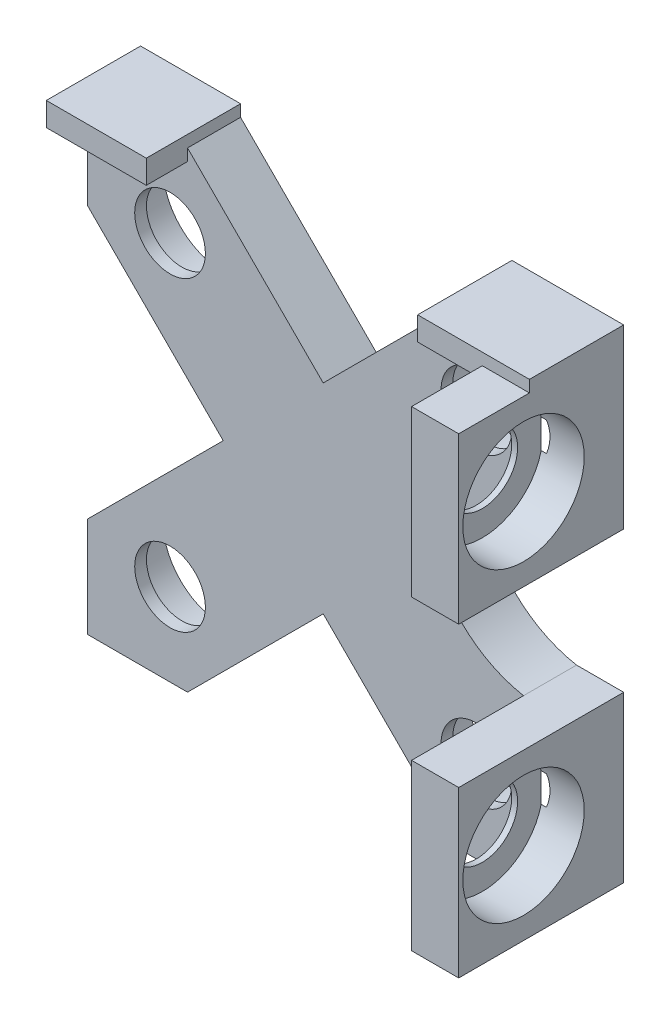
SolidWorks part; units mm, degrees
ref_plane "Plano frontal" through (0, 0, 0) normal (0, 0, 1) x (1, 0, 0)
ref_plane "Plano superior" through (0, 0, 0) normal (0, 1, 0) x (1, 0, 0)
ref_plane "Plano direito" through (0, 0, 0) normal (1, 0, 0) x (0, 0, -1)
sketch "Esboço1" plane through (0, 0, 0) normal (0, 0, 1) x (1, 0, 0)
  line L0 (-8.4853, 0) -> (-20, 11.5147)
  line L1 (-11.5147, 20) -> (-20, 20)
  line L2 (-11.5147, 20) -> (0, 8.4853)
  line L3 (0, 8.4853) -> (0, 0)
  line L4 (0, 0) -> (-8.4853, 0)
  line L5 (-20, 20) -> (-20, 11.5147)
  point P1 (7.079, 9.8915)
  point P3 (0, 0)
  dimension "D1" = 12
  dimension "D2" = 45
  dimension "D3" = 20
extrude "Ressalto-extrusão1" add sketch "Esboço1" along normal blind 4.5
sketch "Esboço2" plane through (0, 0, 4.5) normal (0, 0, 1) x (1, 0, 0)
  line L0 (-20, 20) -> (0, 0) construction
  line L1 (0, 0) -> (0, 8.4853) construction
  circle A0 centre (-13, 13) radius 5.1
  point P6 (-6.6212, 15.1064)
  point P7 (-5.3132, 13.7985)
  dimension "D1" = 10.2
  dimension "D2" = 13
extrude "Corte-extrusão1" cut sketch "Esboço2" along normal blind 3.5 from surface at -4.5 starting at face at (-10, 10, 0)
sketch "Esboço3" plane through (0, 0, 3.5) normal (0, 0, -1) x (-1, 0, 0)
  circle A0 centre (13, 13) radius 3
  dimension "D1" = 6
extrude "Corte-extrusão2" cut sketch "Esboço3" against normal blind 3.5
mirror "Espelhar1" about plane through (0, 0, 0) normal (1, 0, 0) of "Corte-extrusão2", "Corte-extrusão1", "Ressalto-extrusão1"
mirror "Espelhar2" about plane through (0, 0, 0) normal (0, 1, 0) of "Corte-extrusão2", "Ressalto-extrusão1", "Corte-extrusão1", "Espelhar1"
sketch "Esboço5" plane through (20, 0, 0) normal (1, 0, 0) x (0, 0, -1)
  line L0 (-4.5, 20) -> (-4.5, 11.5147) construction
  line L1 (0, 20) -> (-14, 20)
  line L2 (0, 20) -> (0, 6)
  line L3 (0, 6) -> (-14, 6)
  line L4 (-14, 20) -> (-14, 6)
  circle A0 centre (-8.5, 13) radius 5 construction
  point P7 (-10.4977, 13)
  point P8 (0, 0)
  dimension "D2" = 10
  dimension "D1" = 13
  dimension "D3" = 14
  dimension "D4" = 4
  dimension "D5" = 14
extrude "Ressalto-extrusão2" add sketch "Esboço5" along normal blind 1 and the other way blind 3
sketch "Esboço6" plane through (21, 0, 0) normal (-1, 0, 0) x (0, 0, 1)
  circle A1 centre (8.5, 13) radius 5.15
  dimension "D1" = 10.3
extrude "Corte-extrusão3" cut sketch "Esboço6" along normal blind 3.5
sketch "Esboço7" plane through (17.5, 0, 0) normal (1, 0, 0) x (0, 0, -1)
  circle A0 centre (-8.5, 13) radius 3
  dimension "D1" = 6
extrude "Corte-extrusão4" cut sketch "Esboço7" against normal through all both and the other way through all
mirror "Espelhar3" about plane through (0, 0, 0) normal (0, 1, 0) of "Corte-extrusão3", "Corte-extrusão4", "Ressalto-extrusão2"
fillet "Filete1" radius 10 2 edges at (17, 8.5147, 2.25) (17, -8.5147, 2.25)
sketch "Esboço8" plane through (0, 20, 0) normal (0, 1, 0) x (1, 0, 0)
  line L0 (21, 0) -> (21, -14) construction
  line L1 (-20, 0) -> (-11.5147, 0)
  line L2 (-20, 0) -> (-20, -8)
  line L3 (-20, -8) -> (-11.5147, -8)
  line L4 (-11.5147, 0) -> (-11.5147, -8)
  line L5 (11.5147, 0) -> (21, 0)
  line L6 (11.5147, 0) -> (11.5147, -8)
  line L7 (11.5147, -8) -> (21, -8)
  line L8 (21, 0) -> (21, -8)
  point P12 (-11.5147, 0)
  dimension "D1" = 8
extrude "Ressalto-extrusão3" add sketch "Esboço8" along normal blind 1 and the other way blind 1
mirror "Espelhar4" about plane through (0, 0, 0) normal (1, 0, 0) of "Corte-extrusão1"
mirror "Espelhar5" about plane through (0, 0, 0) normal (0, 1, 0) of "Espelhar4"
